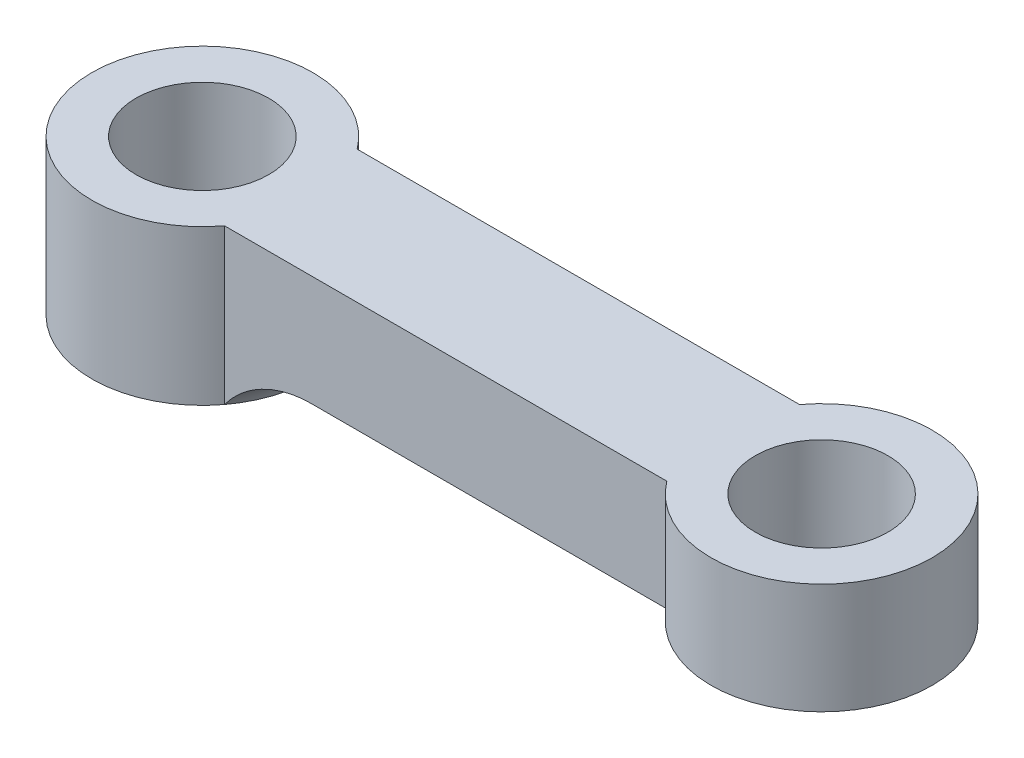
SolidWorks part; units mm, degrees
ref_plane "Front Plane" through (0, 0, 0) normal (0, 0, 1) x (1, 0, 0)
ref_plane "Top Plane" through (0, 0, 0) normal (0, 1, 0) x (1, 0, 0)
ref_plane "Right Plane" through (0, 0, 0) normal (1, 0, 0) x (0, 0, -1)
sketch "Sketch2" plane through (0, 0, 0) normal (0, 1, 0) x (1, 0, 0)
  line L0 (0, 0) -> (-16, 0)
  line L1 (-16, 0) -> (-14, 0)
  line L2 (-14, 0) -> (-14, 2)
  line L3 (-14, 2) -> (-14, -2)
  line L4 (-14, -2) -> (0, -2)
  line L5 (0, -2) -> (0, 2)
  line L6 (0, 2) -> (-14, 2)
  line L7 (0, 0) -> (0, 1.5)
  line L8 (0, 1.5) -> (-12.6771, 1.5)
  line L9 (-12.6771, 1.5) -> (-12.6771, -1.5)
  line L10 (-12.6771, -1.5) -> (0, -1.5)
  circle A0 centre (-14, 0) radius 1.5
  circle A1 centre (-14, 0) radius 2
  dimension "D1" = 16
extrude "Boss-Extrude1" add sketch "Sketch2" along normal blind 10 contours A1 L10 L5 L0 | A1 L0 L5 L8 | L9 A1 L0 A0 | L0 A1 L9 A0 | L3 A1 L9 A0 | L1 A1 L3 A0 | L3 A1 L1 A0 | L9 A1 L3 A0
sketch "Sketch3" plane through (0, 10, 0) normal (0, 1, 0) x (1, 0, 0)
  circle A0 centre (-14, 0) radius 2.5
  circle A1 centre (-14, 0) radius 2
extrude "Boss-Extrude2" add sketch "Sketch3" against normal blind 10
other "Move Face1" face at (-7.125, 10, 0) parameters "D1"=5
sketch "Sketch4" plane through (0, 5, 0) normal (0, 1, 0) x (1, 0, 0)
  circle A0 centre (0, 0) radius 1.5
  circle A1 centre (0, 0) radius 2.5
extrude "Boss-Extrude3" add sketch "Sketch4" against normal blind 5
sketch "Sketch5" plane through (0, 5, 0) normal (0, 1, 0) x (1, 0, 0)
  circle A0 centre (0, 0) radius 1.5
extrude "Cut-Extrude1" cut sketch "Sketch5" against normal blind 5
other "Move Face2" face at (0, 5, 1.5) parameters "D1"=1
sketch "Sketch11" plane through (0, 4, 0) normal (0, 1, 0) x (1, 0, 0)
  line L0 (-7, 1.5) -> (-7, -1.5)
  line L1 (-2, 1.5) -> (-12, 1.5) construction
  line L2 (-12, -1.5) -> (-2, -1.5) construction
  line L3 (-7, -1.5) -> (-7, 0)
  line L4 (-7, 0) -> (-3, 0)
  line L5 (-3, 0) -> (-3, 1.5)
  line L6 (-3, 1.5) -> (-3, -1.5)
  line L7 (-7, 0) -> (-11, 0)
  line L8 (-11, 0) -> (-11, 1.5)
  line L9 (-11, 1.5) -> (-11, -1.5)
  circle M1 centre (0, 0) radius 1.5
  arc M2 (-2, -1.5) -> (-2, 1.5) centre (0, 0) ccw
  line M3 (-2, 1.5) -> (-12, 1.5)
  arc M4 (-12, 1.5) -> (-12, -1.5) centre (-14, 0) ccw
  line M5 (-12, -1.5) -> (-2, -1.5)
  circle M6 centre (-14, 0) radius 1.5
extrude "Cut-Extrude2" cut sketch "Sketch11" against normal blind 0.75 contours L9 L8 M3 M4 M5 M6 | L5 L6 M5 M2 M3 M1
sketch "Sketch12" plane through (0, 0, 0) normal (0, -1, 0) x (-1, 0, 0)
  line L0 (7, -1.5) -> (7, 1.5)
  line L1 (12, -1.5) -> (2, -1.5) construction
  line L2 (2, 1.5) -> (12, 1.5) construction
  line L3 (7, 1.5) -> (11, 1.5)
  line L4 (11, 1.5) -> (11, -1.5)
  line L5 (11, -1.5) -> (7, -1.5)
  line L6 (7, 1.5) -> (3, 1.5)
  line L7 (3, 1.5) -> (3, -1.5)
  line L8 (3, -1.5) -> (7, -1.5)
  line L9 (7, 1.5) -> (3, 1.5)
  line M1 (12, 1.5) -> (2, 1.5)
  arc M2 (2, 1.5) -> (2, -1.5) centre (0, 0) ccw
  line M3 (2, -1.5) -> (12, -1.5)
  arc M4 (12, -1.5) -> (12, 1.5) centre (14, 0) ccw
  circle M5 centre (0, 0) radius 1.5
  circle M6 centre (14, 0) radius 1.5
extrude "Cut-Extrude3" cut sketch "Sketch12" against normal blind 0.75 contours L4 M1 M3 M4 M6 | L7 M1 M2 M3 M5
fillet "Fillet1" radius 1 4 edges at (-3, 0, 0) (-3, 4, 0) (-11, 0, 0) (-11, 4, 0)
sketch "Sketch13" plane through (0, 0, 0) normal (0, -1, 0) x (-1, 0, 0)
  line L1 (11, 1.5) -> (3, 1.5)
  line L2 (11, 1.5) -> (11, -1.5)
  line L3 (11, -1.5) -> (3, -1.5)
  line L4 (3, 1.5) -> (3, -1.5)
extrude "Cut-Extrude4" cut sketch "Sketch13" against normal blind 0.75
sketch "Sketch14" plane through (0, 4, 0) normal (0, 1, 0) x (1, 0, 0)
  line L1 (-11, -1.5) -> (-3, -1.5)
  line L2 (-11, -1.5) -> (-11, 1.5)
  line L3 (-11, 1.5) -> (-3, 1.5)
  line L4 (-3, -1.5) -> (-3, 1.5)
extrude "Cut-Extrude5" cut sketch "Sketch14" against normal blind 0.75
sketch "Sketch16" plane through (0, 0.75, 0) normal (0, -1, 0) x (-1, 0, 0)
  circle A0 centre (14, 0) radius 1.5
  circle A1 centre (14, 0) radius 2.5
extrude "Boss-Extrude6" add sketch "Sketch16" along normal blind 1
fillet "Fillet3" radius 2 1 edges at (-11.5, 0.75, 0)
